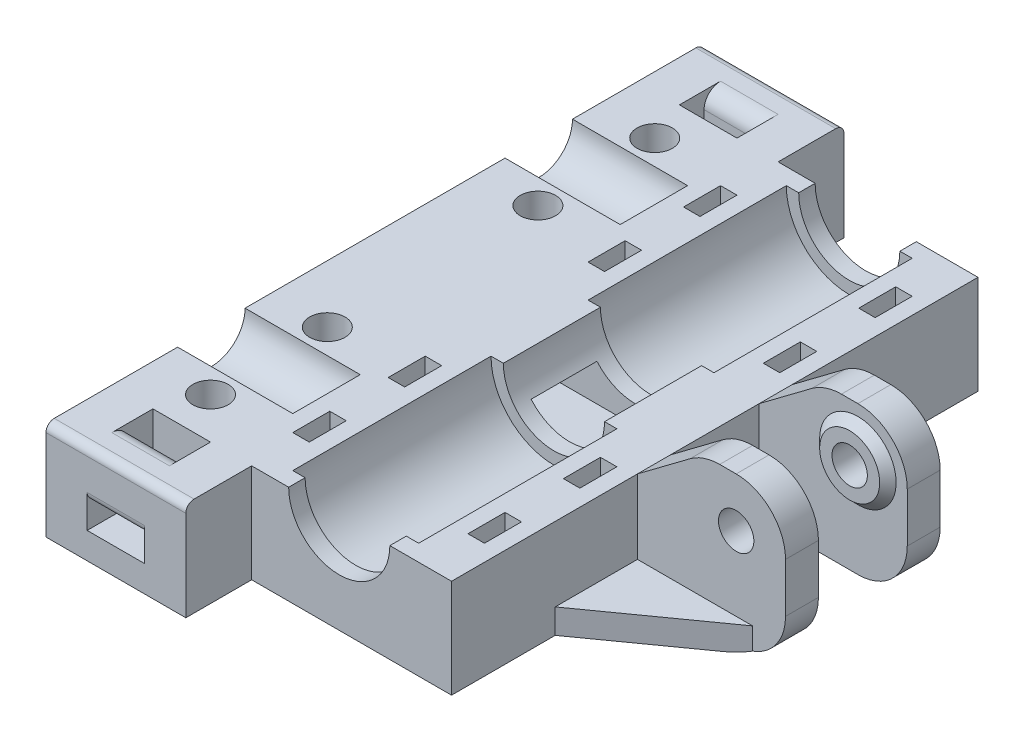
SolidWorks part; units mm, degrees
ref_plane "Alzado" through (0, 0, 0) normal (0, 0, 1) x (1, 0, 0)
ref_plane "Planta" through (0, 0, 0) normal (0, 1, 0) x (1, 0, 0)
ref_plane "Vista lateral" through (0, 0, 0) normal (1, 0, 0) x (0, 0, -1)
sketch "Croquis1" plane through (0, 0, 0) normal (0, 0, 1) x (1, 0, 0)
  line L6 (-7.65, 0) -> (-13.65, 0)
  line L7 (-13.65, 0) -> (-13.65, -12)
  line L8 (-13.65, -12) -> (11.65, -12)
  line L9 (11.65, -12) -> (11.65, 0)
  line L10 (11.65, 0) -> (7.65, 0)
  arc A2 (-7.65, 0) -> (7.65, 0) centre (0, 0) ccw
  dimension "D1" = 7.65
  dimension "D2" = 4
  dimension "D3" = 12
  dimension "D4" = 6
extrude "Saliente-Extruir1" add sketch "Croquis1" along normal blind 64
sketch "Croquis2" plane through (0, 0, 64) normal (0, 0, 1) x (1, 0, 0)
  line L0 (-7.65, 0) -> (-6.15, 0)
  line L1 (6.15, 0) -> (7.65, 0)
  arc A0 (-7.65, 0) -> (7.65, 0) centre (0, 0) ccw construction
  arc A1 (-7.65, 0) -> (7.65, 0) centre (0, 0) ccw
  arc A2 (-6.15, 0) -> (6.15, 0) centre (0, 0) ccw
  dimension "D1" = 1.5
extrude "Saliente-Extruir2" add sketch "Croquis2" against normal blind 2
sketch "Croquis3" plane through (0, 0, 0) normal (0, 0, -1) x (-1, 0, 0)
  line L2 (7.65, 0) -> (6.15, 0)
  line L3 (-6.15, 0) -> (-7.65, 0)
  line L4 (7.65, 0) -> (6.15, 0)
  line L5 (-6.15, 0) -> (-7.65, 0)
  arc A2 (-7.65, 0) -> (7.65, 0) centre (0, 0) ccw
  arc A3 (-6.15, 0) -> (6.15, 0) centre (0, 0) ccw
  arc A4 (-7.65, 0) -> (7.65, 0) centre (0, 0) ccw
  arc A5 (-6.15, 0) -> (6.15, 0) centre (0, 0) ccw
  dimension "D1" = 0
extrude "Saliente-Extruir3" add sketch "Croquis3" against normal blind 2
sketch "Croquis4" plane through (0, 0, 2) normal (0, 0, 1) x (1, 0, 0)
  line L2 (7.65, 0) -> (6.15, 0)
  line L3 (-6.15, 0) -> (-7.65, 0)
  line L4 (7.65, 0) -> (6.15, 0)
  line L5 (-6.15, 0) -> (-7.65, 0)
  arc A2 (-7.65, 0) -> (7.65, 0) centre (0, 0) ccw
  arc A3 (-6.15, 0) -> (6.15, 0) centre (0, 0) ccw
  arc A4 (-7.65, 0) -> (7.65, 0) centre (0, 0) ccw
  arc A5 (-6.15, 0) -> (6.15, 0) centre (0, 0) ccw
  dimension "D1" = 0
extrude "Saliente-Extruir4" add sketch "Croquis4" along normal blind 11.8 from offset 24.1
sketch "Croquis5" plane through (-13.65, 0, 0) normal (-1, 0, 0) x (0, 0, 1)
  line L0 (64, 0) -> (0, 0) construction
  line L1 (8, 0) -> (0, 0)
  line L2 (47.8, 0) -> (16.2, 0)
  line L4 (0, 0) -> (0, -12)
  line L5 (0, -12) -> (64, -12)
  line L6 (64, -12) -> (64, 0)
  line L7 (64, 0) -> (0, 0)
  line L8 (0, 0) -> (0, -12)
  line L9 (0, -12) -> (64, -12)
  line L10 (64, -12) -> (64, 0)
  line L11 (64, 0) -> (56, 0)
  arc A0 (8, 0) -> (16.2, 0) centre (12.1, 0) ccw
  arc A1 (56, 0) -> (47.8, 0) centre (51.9, 0) cw
  dimension "D3" = 4.1
  dimension "D2" = 8
  dimension "D4" = 8
  dimension "D1" = 0
extrude "Saliente-Extruir5" add sketch "Croquis5" along normal blind 14
sketch "Croquis6" plane through (0, 0, 0) normal (0, 1, 0) x (1, 0, 0)
  line L0 (-27.65, -8) -> (-27.65, 0) construction
  line L3 (-20.65, -19.2) -> (-20.65, -5) construction
  line L4 (-20.65, -59) -> (-20.65, -44.8) construction
  line L5 (-13.65, -56) -> (-13.65, -47.8) construction
  line L6 (-27.65, -8) -> (-27.65, -16.2) construction
  circle A0 centre (-20.65, -59) radius 2.15
  circle A1 centre (-20.65, -5) radius 2.15
  circle A2 centre (-20.65, -19.2) radius 2.15
  circle A3 centre (-20.65, -44.8) radius 2.15
  point P7 (-20.65, -12.1)
  point P14 (-20.65, -51.9)
  point P17 (-13.65, -51.9)
  point P18 (-27.65, -12.1)
  dimension "D3" = 4.3
  dimension "D1" = 7
  dimension "D2" = 14.2
extrude "Cortar-Extruir1" cut sketch "Croquis6" against normal through all
sketch "Croquis7" plane through (11.65, 0, 0) normal (1, 0, 0) x (0, 0, -1)
  line L5 (-64, 0) -> (0, 0) construction
  line L6 (-36, -4) -> (-28, -4)
  line L7 (-36, -4) -> (-36, -8.5)
  line L8 (-36, -8.5) -> (-28, -8.5)
  line L9 (-28, -4) -> (-28, -8.5)
  point P4 (-32, -4)
  point P7 (-32, 0)
  dimension "D1" = 8.5
  dimension "D2" = 4
  dimension "D3" = 8
extrude "Cortar-Extruir2" cut sketch "Croquis7" against normal through all
sketch "Croquis8" plane through (0, 0, 37.9) normal (0, 0, 1) x (1, 0, 0)
  line L0 (-9.65, 0) -> (-11.65, 0)
  line L1 (-6.15, 0) -> (-27.65, 0) construction
  line L2 (7.65, 0) -> (6.15, 0)
  line L3 (-6.15, 0) -> (-7.65, 0)
  line L4 (7.65, 0) -> (6.15, 0) construction
  line L6 (-11.65, 0) -> (-11.65, -6)
  line L7 (-11.65, -6) -> (-5.65, -12)
  line L8 (-27.65, -12) -> (11.65, -12) construction
  line L9 (-5.65, -12) -> (5.65, -12)
  line L10 (5.65, -12) -> (11.65, -6)
  line L11 (11.65, -12) -> (11.65, 0) construction
  line L12 (11.65, -6) -> (11.65, 0)
  line L13 (11.65, 0) -> (9.65, 0)
  line L14 (11.65, 0) -> (6.15, 0) construction
  line L15 (9.65, 0) -> (9.65, -5.1716)
  line L16 (9.65, -5.1716) -> (4.8216, -10)
  line L17 (4.8216, -10) -> (-4.8216, -10)
  line L18 (-4.8216, -10) -> (-9.65, -5.1716)
  line L19 (-9.65, -5.1716) -> (-9.65, 0)
  line L22 (-6.15, 0) -> (-7.65, 0) construction
  arc A2 (-7.65, 0) -> (7.65, 0) centre (0, 0) ccw
  arc A3 (-6.15, 0) -> (6.15, 0) centre (0, 0) ccw
  arc A5 (-6.15, 0) -> (6.15, 0) centre (0, 0) ccw construction
  arc A6 (-7.65, 0) -> (7.65, 0) centre (0, 0) ccw construction
  point P3 (0, -12)
  point P10 (0, -10)
  dimension "D2" = 2
  dimension "D3" = 2
  dimension "D4" = 2
  dimension "D5" = 45
  dimension "D6" = 6
  dimension "D1" = 0
extrude "Cortar-Extruir3" cut sketch "Croquis8" along normal blind 4.5 from offset 4
fillet "Redondeo1" radius 3 5 edges at (-11.65, -6, 44.15) (-9.65, -5.1716, 44.15) (-4.8216, -10, 44.15) (4.8216, -10, 44.15) (9.65, -5.1716, 44.15)
sketch "Croquis10" plane through (0, 0, 62) normal (0, 0, -1) x (-1, 0, 0)
  line L12 (5.65, -12) -> (10.7713, -6.8787)
  line L13 (11.65, -4.7574) -> (11.65, 0)
  line L14 (11.65, 0) -> (9.65, 0)
  line L15 (9.65, 0) -> (9.65, -3.9289)
  line L16 (8.7713, -6.0503) -> (5.7003, -9.1213)
  line L17 (3.5789, -10) -> (-3.5789, -10)
  line L18 (-5.7003, -9.1213) -> (-8.7713, -6.0503)
  line L19 (-9.65, -3.9289) -> (-9.65, 0)
  line L20 (-9.65, 0) -> (-11.65, 0)
  line L21 (-11.65, 0) -> (-11.65, -6)
  line L22 (-11.65, -6) -> (-5.65, -12)
  line L23 (-5.65, -12) -> (5.65, -12)
  line L24 (5.65, -12) -> (10.7713, -6.8787)
  line L25 (11.65, -4.7574) -> (11.65, 0)
  line L26 (11.65, 0) -> (9.65, 0)
  line L27 (9.65, 0) -> (9.65, -3.9289)
  line L28 (8.7713, -6.0503) -> (5.7003, -9.1213)
  line L29 (3.5789, -10) -> (-3.5789, -10)
  line L30 (-5.7003, -9.1213) -> (-8.7713, -6.0503)
  line L31 (-9.65, -3.9289) -> (-9.65, 0)
  line L32 (-9.65, 0) -> (-11.65, 0)
  line L33 (-11.65, 0) -> (-11.65, -6)
  line L34 (-11.65, -6) -> (-5.65, -12)
  line L35 (-5.65, -12) -> (5.65, -12)
  arc A5 (10.7713, -6.8787) -> (11.65, -4.7574) centre (8.65, -4.7574) ccw
  arc A6 (8.7713, -6.0503) -> (9.65, -3.9289) centre (6.65, -3.9289) ccw
  arc A7 (3.5789, -10) -> (5.7003, -9.1213) centre (3.5789, -7) ccw
  arc A8 (-5.7003, -9.1213) -> (-3.5789, -10) centre (-3.5789, -7) ccw
  arc A9 (-9.65, -3.9289) -> (-8.7713, -6.0503) centre (-6.65, -3.9289) ccw
  arc A10 (10.7713, -6.8787) -> (11.65, -4.7574) centre (8.65, -4.7574) ccw
  arc A11 (8.7713, -6.0503) -> (9.65, -3.9289) centre (6.65, -3.9289) ccw
  arc A12 (3.5789, -10) -> (5.7003, -9.1213) centre (3.5789, -7) ccw
  arc A13 (-5.7003, -9.1213) -> (-3.5789, -10) centre (-3.5789, -7) ccw
  arc A14 (-9.65, -3.9289) -> (-8.7713, -6.0503) centre (-6.65, -3.9289) ccw
  dimension "D1" = 0
extrude "Cortar-Extruir4" cut sketch "Croquis10" along normal blind 4.5 from offset 4
ref_plane "Plano1" through (0, 0, 32) normal (0, 0, -1) x (-1, 0, 0)
mirror "Simetría1" about plane through (0, 0, 32) normal (0, 0, -1) of "Redondeo1", "Cortar-Extruir4", "Cortar-Extruir3"
sketch "Croquis11" plane through (0, -12, 0) normal (0, -1, 0) x (1, 0, 0)
  line L1 (-16.5508, 5) -> (-18.6004, 8.55)
  line L2 (-18.6004, 8.55) -> (-22.6996, 8.55)
  line L3 (-22.6996, 8.55) -> (-24.7492, 5)
  line L4 (-24.7492, 5) -> (-22.6996, 1.45)
  line L5 (-22.6996, 1.45) -> (-18.6004, 1.45)
  line L6 (-18.6004, 1.45) -> (-16.5508, 5)
  line L7 (-16.5508, 19.2) -> (-18.6004, 22.75)
  line L8 (-18.6004, 22.75) -> (-22.6996, 22.75)
  line L9 (-22.6996, 22.75) -> (-24.7492, 19.2)
  line L10 (-24.7492, 19.2) -> (-22.6996, 15.65)
  line L11 (-22.6996, 15.65) -> (-18.6004, 15.65)
  line L12 (-18.6004, 15.65) -> (-16.5508, 19.2)
  line L13 (-16.5508, 44.8) -> (-18.6004, 48.35)
  line L14 (-18.6004, 48.35) -> (-22.6996, 48.35)
  line L15 (-22.6996, 48.35) -> (-24.7492, 44.8)
  line L16 (-24.7492, 44.8) -> (-22.6996, 41.25)
  line L17 (-22.6996, 41.25) -> (-18.6004, 41.25)
  line L18 (-18.6004, 41.25) -> (-16.5508, 44.8)
  line L19 (-16.5508, 59) -> (-18.6004, 62.55)
  line L20 (-18.6004, 62.55) -> (-22.6996, 62.55)
  line L21 (-22.6996, 62.55) -> (-24.7492, 59)
  line L22 (-24.7492, 59) -> (-22.6996, 55.45)
  line L23 (-22.6996, 55.45) -> (-18.6004, 55.45)
  line L24 (-18.6004, 55.45) -> (-16.5508, 59)
  circle A0 centre (-20.65, 5) radius 3.55 construction
  circle A1 centre (-20.65, 19.2) radius 3.55 construction
  circle A2 centre (-20.65, 44.8) radius 3.55 construction
  circle A3 centre (-20.65, 59) radius 3.55 construction
  dimension "D1" = 7.1
extrude "Cortar-Extruir5" cut sketch "Croquis11" against normal blind 4
sketch "Croquis13" plane through (0, 0, 0) normal (0, 1, 0) x (1, 0, 0)
  line L1 (-27.65, -64) -> (-10.65, -64)
  line L2 (-27.65, -64) -> (-27.65, -72)
  line L3 (-27.65, -72) -> (-10.65, -72)
  line L4 (-10.65, -64) -> (-10.65, -72)
  dimension "D1" = 8
  dimension "D2" = 17
extrude "Saliente-Extruir6" add sketch "Croquis13" against normal up to surface (12 mm away) up to face at (-20.65, -12, 5)
sketch "Croquis14" plane through (-10.65, 0, 0) normal (1, 0, 0) x (0, 0, -1)
  line L0 (-72, -5.8) -> (-67, -5.8)
  line L1 (-72, -12) -> (-72, 0) construction
  line L2 (-67, -5.8) -> (-67, 0)
  line L3 (-72, 0) -> (-64, 0) construction
  line L4 (-67, 0) -> (-64, 0)
  line L5 (-64, 0) -> (-64, -8.8)
  line L6 (-64, -12) -> (-64, 0) construction
  line L7 (-64, -8.8) -> (-72, -8.8)
  line L8 (-72, -8.8) -> (-72, -5.8)
  dimension "D1" = 3
  dimension "D2" = 5.8
  dimension "D3" = 3
extrude "Cortar-Extruir6" cut sketch "Croquis14" against normal blind 7 from offset 5 offset against normal yes
fillet "Redondeo2" radius 2 2 edges at (-19.15, -5.8, 67) (-19.15, 0, 67)
fillet "Redondeo3" radius 1 2 edges at (-19.15, 0, 72) (-19.15, -5.8, 72)
mirror "Simetría2" about plane through (0, 0, 32) normal (0, 0, -1) of "Redondeo3", "Redondeo2", "Cortar-Extruir6", "Saliente-Extruir6"
sketch "Croquis15" plane through (11.65, 0, 0) normal (1, 0, 0) x (0, 0, -1)
  line L0 (-28, -8.5) -> (-28, -4) construction
  line L1 (0, 0) -> (-64, 0)
  line L2 (0, 0) -> (0, -12)
  line L3 (0, -12) -> (-64, -12)
  line L4 (-64, 0) -> (-64, -12)
  line L5 (-28, -4) -> (-36, -4) construction
  line L6 (-36, -4) -> (-36, -8.5) construction
  line L7 (-36, -8.5) -> (-28, -8.5) construction
  line L8 (-28, -8.5) -> (-28, -4)
  line L9 (-28, -4) -> (-36, -4)
  line L10 (-36, -4) -> (-36, -8.5)
  line L11 (-36, -8.5) -> (-28, -8.5)
extrude "Saliente-Extruir7" add sketch "Croquis15" along normal blind 2
sketch "Croquis16" plane through (0, 0, 32) normal (0, 0, -1) x (-1, 0, 0)
  line L6 (-13.65, 0) -> (-21.65, 6)
  line L7 (-21.65, 6) -> (-31.65, 6)
  line L8 (-31.65, 6) -> (-31.65, -12)
  line L9 (-31.65, -12) -> (-13.65, -12)
  line L10 (-13.65, -12) -> (-13.65, 0) construction
  line L11 (-13.65, -12) -> (-13.65, 0)
  circle A1 centre (-25.65, 0) radius 2.15
  dimension "D6" = 4.3
  dimension "D8" = 6
  dimension "D7" = 12
  dimension "D9" = 6
  dimension "D10" = 8
extrude "Saliente-Extruir8" add sketch "Croquis16" along normal blind 4 from offset 5.4
sketch "Croquis17" plane through (0, -12, 0) normal (0, -1, 0) x (1, 0, 0)
  line L5 (13.65, 22.6) -> (13.65, 12.6)
  line L6 (13.65, 22.6) -> (13.65, 0) construction
  line L7 (13.65, 12.6) -> (27.65, 22.6)
  line L8 (31.65, 22.6) -> (13.65, 22.6) construction
  line L9 (27.65, 22.6) -> (13.65, 22.6)
  line L10 (31.65, 22.6) -> (31.65, 26.6) construction
  dimension "D3" = 4
  dimension "D4" = 10
extrude "Saliente-Extruir9" add sketch "Croquis17" against normal blind 3
fillet "Redondeo4" radius 6 3 edges at (31.65, 6, 24.6) (31.65, -12, 24.6) (21.65, 6, 24.6)
sketch "Croquis18" plane through (0, 0, 26.6) normal (0, 0, 1) x (1, 0, 0)
  circle A0 centre (25.65, 0) radius 3.65
  circle A1 centre (25.65, 0) radius 2.15 construction
  circle A2 centre (25.65, 0) radius 2.15
  dimension "D1" = 1.5
extrude "Saliente-Extruir10" add sketch "Croquis18" along normal blind 1
chamfer "Chaflán1" distance 1 angle 45 1 edges at (22, 0, 26.6)
mirror "Simetría3" about plane through (0, 0, 32) normal (0, 0, -1) of "Chaflán1", "Saliente-Extruir10", "Saliente-Extruir9", "Saliente-Extruir8", "Redondeo4"
